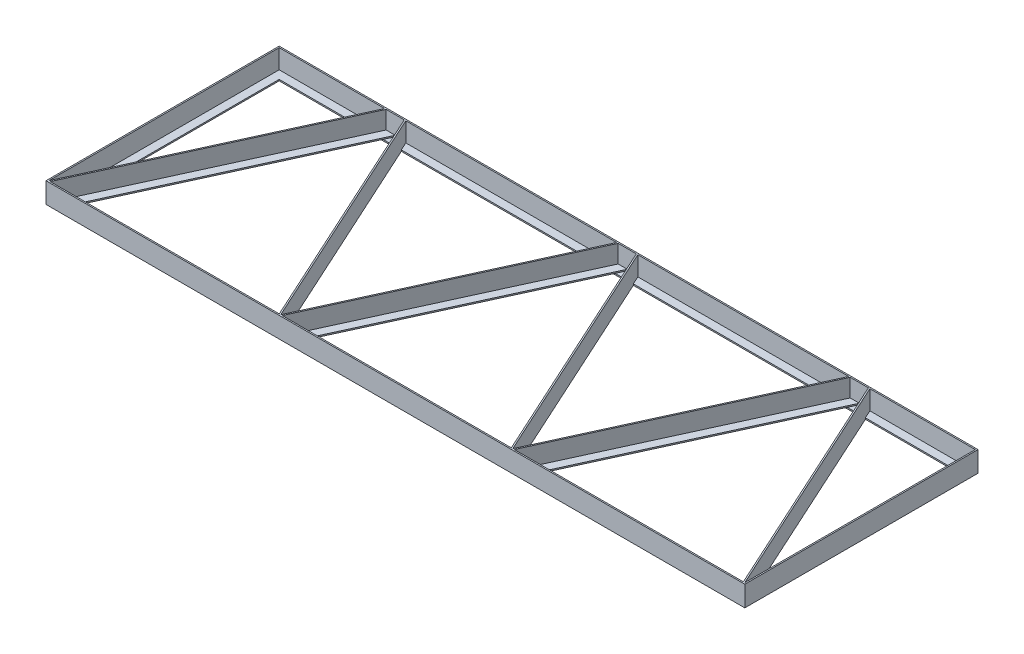
SolidWorks part; units mm, degrees
ref_plane "Front Plane" through (0, 0, 0) normal (0, 0, 1) x (1, 0, 0)
ref_plane "Top Plane" through (0, 0, 0) normal (0, 1, 0) x (1, 0, 0)
ref_plane "Right Plane" through (0, 0, 0) normal (1, 0, 0) x (0, 0, -1)
sketch "Sketch1" plane through (0, 0, 0) normal (0, 1, 0) x (1, 0, 0)
  line L0 (0, 0) -> (1812, 0)
  line L1 (0, -600) -> (1812, -600)
  line L2 (0, 0) -> (0, -600)
  line L3 (1812, 0) -> (1812, -600)
  line L4 (0, -600) -> (274.5078, 0)
  line L5 (0, -600) -> (27.4922, -600)
  line L6 (274.5078, 0) -> (302, 0)
  line L7 (27.4922, -600) -> (302, 0)
  line L8 (0, -600) -> (302, 0) construction
  line L9 (274.5078, 0) -> (27.4922, -600) construction
  line L10 (302, 0) -> (302, -600) construction
  line L11 (3.8269, -600) -> (278.3347, 0)
  line L12 (600.1731, -600) -> (325.6653, 0)
  line L13 (576.5078, -600) -> (302, 0)
  line L14 (604, -600) -> (329.4922, 0)
  line L15 (631.4922, -600) -> (906, 0)
  line L16 (607.8269, -600) -> (882.3347, 0)
  line L17 (604, -600) -> (878.5078, 0)
  line L18 (1180.5078, -600) -> (906, 0)
  line L19 (1204.1731, -600) -> (929.6653, 0)
  line L20 (1208, -600) -> (933.4922, 0)
  line L21 (1235.4922, -600) -> (1510, 0)
  line L22 (1211.8269, -600) -> (1486.3347, 0)
  line L23 (1208, -600) -> (1482.5078, 0)
  line L24 (1784.5078, -600) -> (1510, 0)
  line L25 (1808.1731, -600) -> (1533.6653, 0)
  line L26 (1812, -600) -> (1537.4922, 0)
  line L35 (-3.48, -603.48) -> (1815.48, -603.48)
  line L36 (1815.48, 3.48) -> (1815.48, -603.48)
  line L37 (-3.48, 3.48) -> (1815.48, 3.48)
  line L38 (-3.48, 3.48) -> (-3.48, -603.48)
  line L40 (21.52, -578.48) -> (1790.48, -578.48)
  line L41 (1790.48, -21.52) -> (1790.48, -578.48)
  line L42 (21.52, -21.52) -> (1790.48, -21.52)
  line L43 (21.52, -21.52) -> (21.52, -578.48)
  point P5 (604, -600)
  point P6 (1208, -600)
  point P7 (302, 0)
  point P10 (906, 0)
  point P11 (1510, 0)
  point P14 (151, -300)
  dimension "D2" = 600
  dimension "D4" = 1812
  dimension "D5" = 302
  dimension "D7" = 25
  dimension "D8" = 3.48
  dimension "D11" = 3.48
  dimension "D12" = 25
  dimension "D3" = 2
  dimension "D6" = 3
  dimension "D9" = 3
extrude "Boss-Extrude2" add sketch "Sketch1" along normal blind 53.48 contours L4 L43 L11 L42 | L43 L4 L1 L11 | L4 L42 L11 L0 | L42 L12 L40 L14 | L12 L42 L14 L0 | L40 L12 L1 L14 | L40 L17 L1 L16 | L42 L17 L40 L16 | L17 L42 L16 L0 | L19 L42 L20 L0 | L42 L19 L40 L20 | L40 L19 L1 L20 | L40 L23 L1 L22 | L42 L23 L40 L22 | L23 L42 L22 L0 | L25 L42 L26 L0 | L42 L25 L41 L26 | L26 L41 L25 L1 | L37 L38 L35 L36 L0 L6 L3 L1 L5 L2 region at (271.4984, 0, 10.76) region at (11.6856, 0, 578.5047) region at (144.0503, 0, 289.3381) region at (332.5016, 0, 10.76) region at (464.8327, 0, 300) region at (597.1637, 0, 589.24) region at (875.4984, 0, 10.76) region at (610.8363, 0, 589.24) region at (743.1673, 0, 300) region at (936.5016, 0, 10.76) region at (1068.8327, 0, 300) region at (1201.1637, 0, 589.24) region at (1479.4984, 0, 10.76) region at (1214.8363, 0, 589.24) region at (1347.1673, 0, 300) region at (1540.5016, 0, 10.76) region at (1667.9497, 0, 289.3381) region at (1800.3144, 0, 578.5047) region at (-1.5624, 0, 300)
extrude "Boss-Extrude9" add sketch "Sketch1<7>" along normal blind 3.48 contours L40 L7 L1 L13 | L43 L42 L4 L0 L2 | L40 L15 L1 L18 | L40 L21 L1 L24 | L26 L42 L41 L3 L0 | L40 L20 L23 | L40 L14 L17 | L20 L42 L23 L0 | L21 L42 L24 | L15 L42 L18 | L14 L42 L17 L0 | L7 L42 L13 region at (137.2539, 0, 6.5981) region at (302, 0, 14.3467) region at (302, 0, 589.3055) region at (604, 0, 10.6945) region at (604, 0, 585.6533) region at (906, 0, 14.3467) region at (906, 0, 589.3055) region at (1208, 0, 10.6945) region at (1208, 0, 585.6533) region at (1510, 0, 14.3467) region at (1510, 0, 589.3055) region at (1674.7461, 0, 6.5981)
sketch "Sketch1<7>" plane through (0, 0, 0) normal (0, 1, 0) x (1, 0, 0) same geometry as "Sketch1"
extrude "Boss-Extrude10" add sketch "Sketch1<9>" along normal blind 6.96 contours L25 L41 L40 L24 L1 | L40 L22 L1 L21 | L40 L18 L1 L19 | L40 L16 L1 L15 | L40 L13 L1 L12 | L43 L11 L5 L7 L40 | L11 L42 L7 L6 | L13 L42 L12 L0 | L18 L42 L19 L0 | L16 L42 L15 L0 | L24 L42 L25 L0 | L22 L42 L21 L0 region at (285.2445, 0, 10.76) region at (20.3865, 0, 587.3167) region at (318.7555, 0, 10.76) region at (583.4176, 0, 589.24) region at (889.2445, 0, 10.76) region at (624.5824, 0, 589.24) region at (922.7555, 0, 10.76) region at (1187.4176, 0, 589.24) region at (1493.2445, 0, 10.76) region at (1228.5824, 0, 589.24) region at (1526.7555, 0, 10.76) region at (1791.6135, 0, 587.3167)
sketch "Sketch1<9>" plane through (0, 0, 0) normal (0, 1, 0) x (1, 0, 0) same geometry as "Sketch1"
extrude "Boss-Extrude11" add sketch "Sketch1<10>" against normal blind 3.48 from surface contours L11 L43 L40 L7 L42 | L42 L13 L40 L12 | L42 L16 L40 L15 | L42 L18 L40 L19 | L42 L22 L40 L21 | L42 L24 L40 L41 L25 region at (153.6012, 0, 298.6001) region at (451.0865, 0, 300) region at (756.9135, 0, 300) region at (1055.0865, 0, 300) region at (1360.9135, 0, 300) region at (1658.3988, 0, 298.6001) starting at face at (318.7555, 6.96, 10.76)
sketch "Sketch1<10>" plane through (0, 0, 0) normal (0, 1, 0) x (1, 0, 0) same geometry as "Sketch1"
